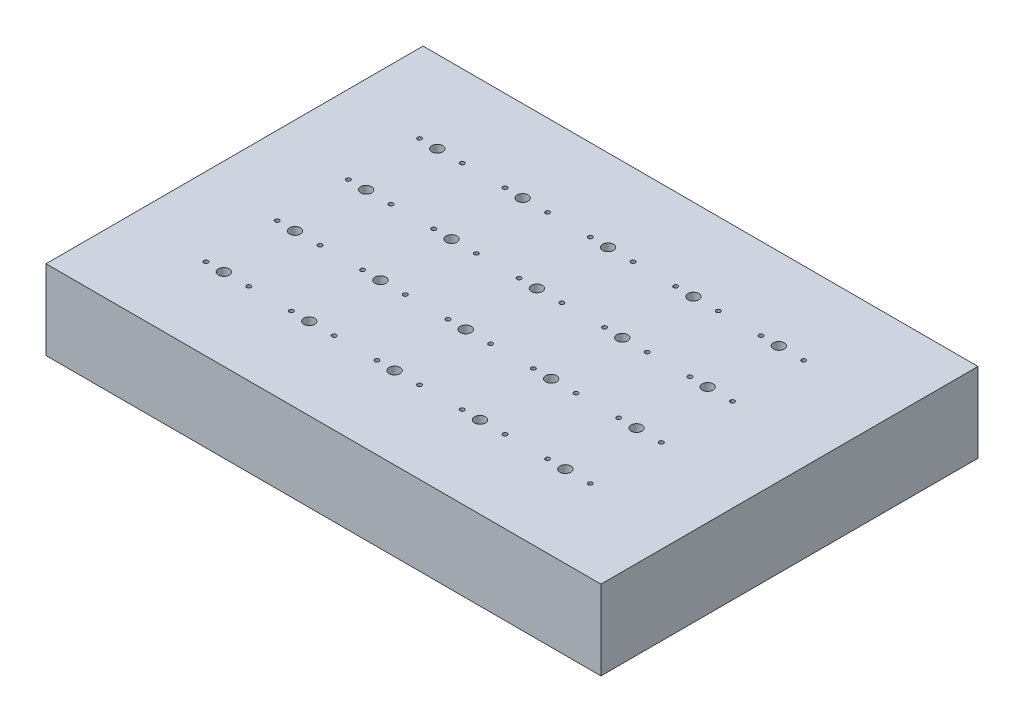
SolidWorks part; units mm, degrees
ref_plane "Front Plane" through (0, 0, 0) normal (0, 0, 1) x (1, 0, 0)
ref_plane "Top Plane" through (0, 0, 0) normal (0, 1, 0) x (1, 0, 0)
ref_plane "Right Plane" through (0, 0, 0) normal (1, 0, 0) x (0, 0, -1)
sketch "BaseWith Alignment" plane through (0, 0, 0) normal (0, 1, 0) x (1, 0, 0)
  line L1 (-10, 7.5) -> (60, 7.5)
  line L2 (-10, 7.5) -> (-10, -37.5)
  line L3 (-10, -37.5) -> (60, -37.5)
  line L4 (60, 7.5) -> (60, -37.5)
  dimension "D3" = 7.5
  dimension "D1" = 70
  dimension "D2" = 45
  dimension "D10" = 10
extrude "Boss-Extrude1" add sketch "BaseWith Alignment" along normal blind 3.175
sketch "Sketch1" plane through (0, 0, 0) normal (0, -1, 0) x (-1, 0, 0)
  line L0 (-3, 0) -> (3, 0) construction
  line L1 (-3, 1.25) -> (3, 1.25) construction
  line L2 (-3, -1.25) -> (3, -1.25) construction
  line L22 (0.5, 0) -> (0.3393, 1.2396) construction
  line L23 (2.0179, 1.9614) -> (2.0179, -1.9614) construction
  line L25 (2.0179, -1.9614) -> (-3.1107, -1.2965)
  line L27 (2.0179, 1.9614) -> (-3.1107, 1.2965)
  line L28 (-3.1107, 1.2965) -> (-3.1107, -1.2965) construction
  line L29 (-3, 0) -> (-3.0386, 0.2975) construction
  line L30 (0.3393, 1.2396) -> (0.275, 1.7355) construction
  line L31 (-3.0386, 0.2975) -> (-3.1671, 1.2892) construction
  arc A0 (-3, 1.25) -> (-3, -1.25) centre (-3, 0) ccw construction
  arc A1 (3, -1.25) -> (3, 1.25) centre (3, 0) ccw construction
  circle A2 centre (0.5, 0) radius 0.762
  circle A3 centre (3, 0) radius 0.3
  circle A4 centre (-3, 0) radius 0.3
  arc A7 (-3.1, 0.2828) -> (-2.7, 0) centre (-3, 0) ccw construction
  circle A8 centre (0.5, 0) radius 1.25 construction
  circle A9 centre (0.5, 0) radius 1 construction
  arc A12 (2.0179, 1.9614) -> (2.0179, -1.9614) centre (2.2722, 0) cw
  arc A13 (-3.1107, 1.2965) -> (-3.1107, -1.2965) centre (-2.9426, 0) ccw
  point P2 (0, 0)
  point P25 (2.0179, 0)
  point P29 (-3.0543, 0)
  point P31 (-3.1107, 0)
  dimension "D3" = 0.6
  dimension "D5" = 1.524
  dimension "D6" = 0.6
  dimension "D7" = 2.5
  dimension "D8" = 2
  dimension "D2" = 2.5
  dimension "D4" = 2.5
  dimension "D1" = 3.5
  dimension "D10" = 3.9229
  dimension "D9" = 0.5
  dimension "D11" = 1
extrude "Boss-Extrude2" add sketch "Sketch1" along normal blind 3 contours L25 A13 L27 A12
extrude "Cut-Extrude1" cut sketch "Sketch1<4>" along normal through all both and the other way through all contours A4 | A2 | A3
sketch "Sketch1<4>" plane through (0, 0, 0) normal (0, -1, 0) x (-1, 0, 0) same geometry as "Sketch1"
pattern_linear "LPattern1" count 4 spacing 10 along (0, 0, 1) count 5 spacing 12 along (1, 0, 0) of "Cut-Extrude1", "Boss-Extrude2"
sketch "Sketch2" plane through (0, 0, 0) normal (0, -1, 0) x (1, 0, 0)
  line L0 (-10, -7.5) -> (-10, 37.5) construction
  line L1 (60, -7.5) -> (-10, -7.5) construction
  line L2 (60, 37.5) -> (60, -7.5) construction
  line L3 (-10, 37.5) -> (60, 37.5) construction
  line L4 (-10, -7.5) -> (-10, 37.5)
  line L5 (60, -7.5) -> (-10, -7.5)
  line L6 (60, 37.5) -> (60, -7.5)
  line L7 (-10, 37.5) -> (60, 37.5)
  line L9 (-14, 41.5) -> (64, 41.5)
  line L10 (-14, 41.5) -> (-14, -11.5)
  line L11 (-14, -11.5) -> (64, -11.5)
  line L12 (64, 41.5) -> (64, -11.5)
  dimension "D1" = 4
  dimension "D2" = 4
  dimension "D3" = 4
  dimension "D4" = 4
extrude "Boss-Extrude3" add sketch "Sketch2" against normal up to surface (3.175 mm away) and the other way blind 8 up to face at (21, 3.175, 9.7)
equation "\"StabilizerRodeHole\"=0.6"
equation "\"D3@Sketch1\"=\"StabilizerRodeHole\""
equation "\"D6@Sketch1\"=\"StabilizerRodeHole\""
